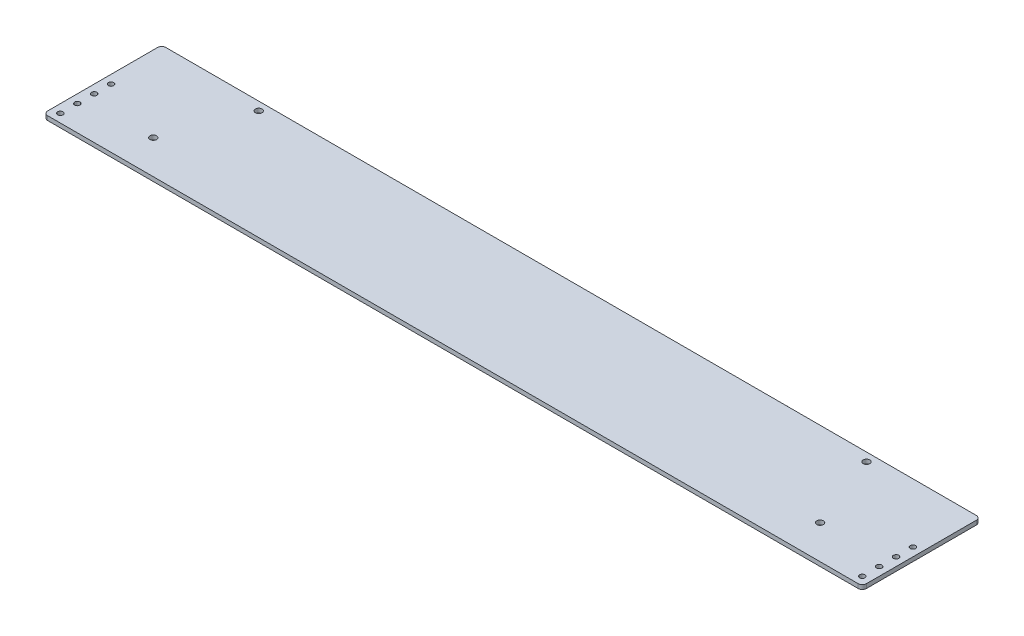
SolidWorks part; units mm, degrees
ref_plane "Front Plane" through (0, 0, 0) normal (0, 0, 1) x (1, 0, 0)
ref_plane "Top Plane" through (0, 0, 0) normal (0, 1, 0) x (1, 0, 0)
ref_plane "Right Plane" through (0, 0, 0) normal (1, 0, 0) x (0, 0, -1)
sketch "Sketch1" plane through (0, 0, 0) normal (0, 1, 0) x (1, 0, 0)
  line L0 (-301.625, 0) -> (-301.625, -38.1) construction
  line L1 (-307.975, -44.45) -> (307.975, -44.45)
  line L2 (-307.975, -44.45) -> (-307.975, 44.45)
  line L3 (-307.975, 44.45) -> (307.975, 44.45)
  line L4 (307.975, -44.45) -> (307.975, 44.45)
  line L5 (-307.975, -44.45) -> (307.975, 44.45) construction
  line L6 (-307.975, 44.45) -> (307.975, -44.45) construction
  line L7 (0, 44.45) -> (0, -44.45) construction
  circle A2 centre (-301.625, 0) radius 2.0193
  circle A3 centre (-301.625, -12.7) radius 2.0193
  circle A4 centre (-301.625, -25.4) radius 2.0193
  circle A5 centre (-301.625, -38.1) radius 2.0193
  circle A6 centre (301.625, -38.1) radius 2.0193
  circle A7 centre (301.625, -25.4) radius 2.0193
  circle A8 centre (301.625, -12.7) radius 2.0193
  circle A9 centre (301.625, 0) radius 2.0193
  point P0 (0, 0)
  dimension "D3" = 6.35
  dimension "D4" = 4.0386
  dimension "D5" = 4
  dimension "D6" = 44.45
  dimension "D7" = 12.7
  dimension "D1" = 88.9
  dimension "D2" = 615.95
extrude "Boss-Extrude1" add sketch "Sketch1" along normal blind 3.175
fillet "Fillet1" radius 3.175 4 edges at (307.975, 1.5875, 44.45) (-307.975, 1.5875, -44.45) (307.975, 1.5875, -44.45) (-307.975, 1.5875, 44.45)
sketch "Sketch2" plane through (0, 3.175, 0) normal (0, 1, 0) x (1, 0, 0)
  line L0 (304.8, 44.45) -> (-304.8, 44.45) construction
  line L1 (-307.975, 41.275) -> (-307.975, -41.275) construction
  line L2 (-304.8, -44.45) -> (304.8, -44.45) construction
  line L3 (0, 44.45) -> (0, -44.45) construction
  circle A0 centre (-228.6, 38.1) radius 2.4892
  circle A1 centre (-250.825, -19.05) radius 2.4892
  circle A2 centre (-250.825, -19.05) radius 25.4 construction
  circle A3 centre (-228.6, 38.1) radius 25.4 construction
  circle A4 centre (250.825, -19.05) radius 25.4 construction
  circle A5 centre (250.825, -19.05) radius 2.4892
  circle A6 centre (228.6, 38.1) radius 25.4 construction
  circle A7 centre (228.6, 38.1) radius 2.4892
  dimension "D1" = 4.9784
  dimension "D2" = 50.8
  dimension "D3" = 50.8
  dimension "D4" = 6.35
  dimension "D6" = 25.4
  dimension "D7" = 79.375
  dimension "D5" = 57.15
extrude "Cut-Extrude1" cut sketch "Sketch2" against normal through all
